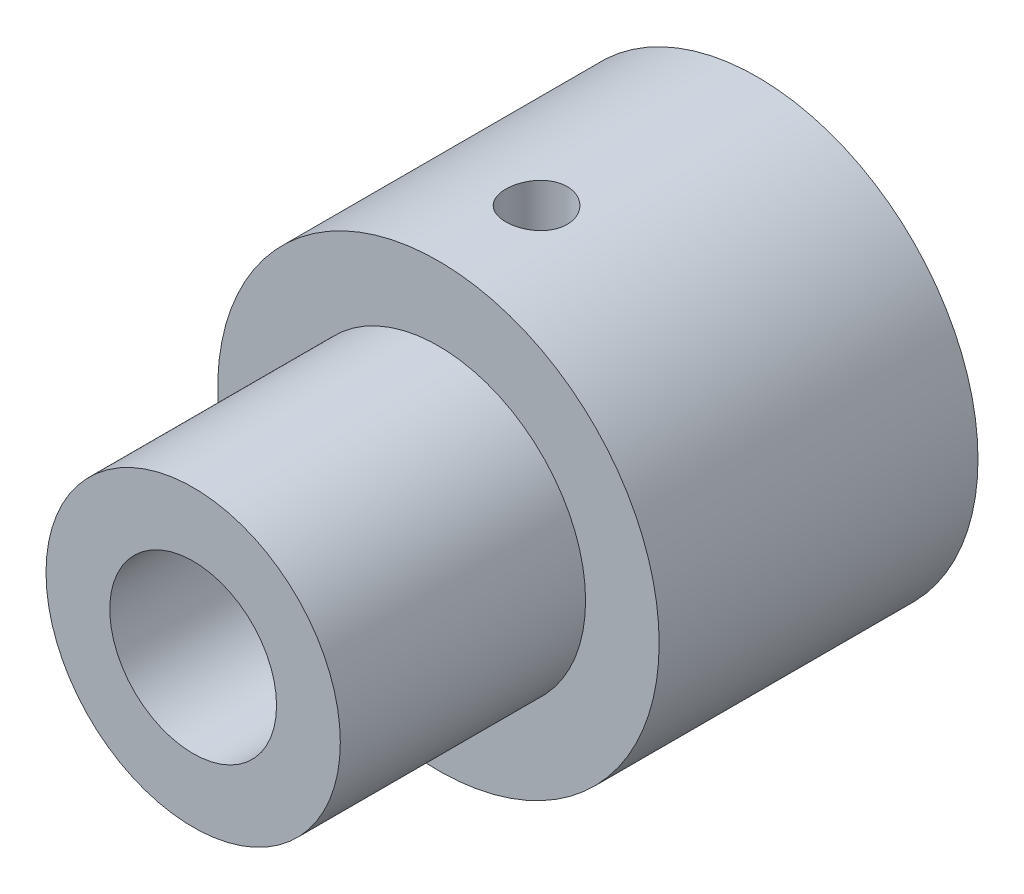
SolidWorks part; units mm, degrees
ref_plane "Front Plane" through (0, 0, 0) normal (0, 0, 1) x (1, 0, 0)
ref_plane "Top Plane" through (0, 0, 0) normal (0, 1, 0) x (1, 0, 0)
ref_plane "Right Plane" through (0, 0, 0) normal (1, 0, 0) x (0, 0, -1)
sketch "Sketch1" plane through (0, 0, 0) normal (1, 0, 0) x (0, 0, -1)
  line L0 (0, 0) -> (10.2668, 0)
  line L1 (10.2668, 0) -> (12.5, 4.2)
  line L2 (12.5, 4.2) -> (23, 4.2)
  line L3 (23, 4.2) -> (23, 9)
  line L4 (23, 9) -> (10, 9)
  line L5 (10, 9) -> (10, 6)
  line L6 (10, 6) -> (0, 6)
  line L7 (0, 6) -> (0, 0)
  line L8 (0, 0) -> (24.188, 0) construction
  dimension "D1" = 10
  dimension "D2" = 13
  dimension "D3" = 6
  dimension "D4" = 2.5
  dimension "D5" = 118
  dimension "D6" = 9
  dimension "D7" = 4.2
revolve "Revolve1" add sketch "Sketch1" angle 360 about L8
sketch "Sketch2" plane through (0, 0, 0) normal (0, 1, 0) x (1, 0, 0)
  line L0 (-6, 10) -> (6, 10) construction
  circle A0 centre (0, 14) radius 1.25
  dimension "D1" = 2.5
  dimension "D2" = 4
extrude "Cut-Extrude1" cut sketch "Sketch2" against normal up to next and the other way up to next
hole_wizard "Tap Drill for M8 Tap1" positions "Sketch4" profile "Sketch3" hole size "M8" standard "ISO"
sketch "Sketch4" plane through (0, 0, 0) normal (0, 0, 1) x (1, 0, 0)
  point P0 (0, 0)
sketch "Sketch3" plane through (0, 0, 0) normal (1, 0, 0) x (0, -1, 0)
  line L0 (0, 0) -> (0, 15.0429)
  line L1 (0, 15.0429) -> (3.4, 13)
  line L2 (3.4, 13) -> (3.4, 0)
  line L5 (3.4, 0) -> (0, 0)
  line L10 (0, 15.0429) -> (-3.4, 13) construction
  line L11 (0, -6.35) -> (0, 107.95) construction
  dimension "Hole Dia." = 6.8
  dimension "Hole Depth" = 13
  dimension "Drill Angle" = 118
